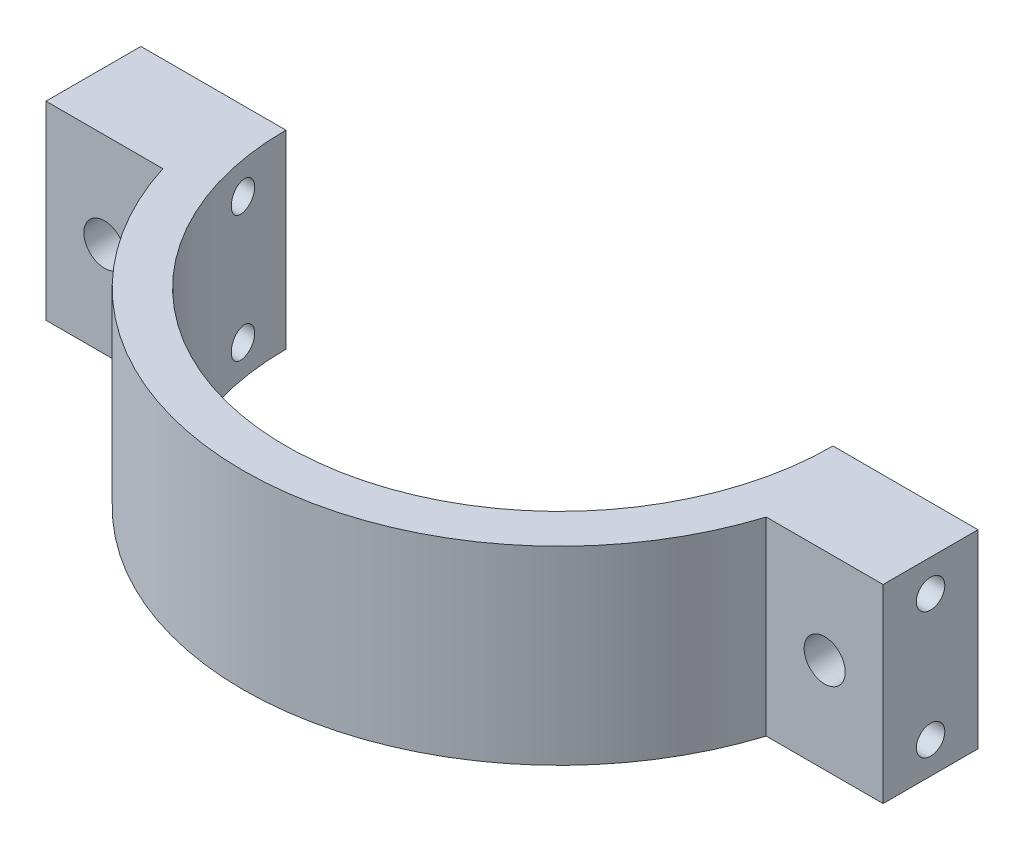
SolidWorks part; units mm, degrees
ref_plane "Front Plane" through (0, 0, 0) normal (0, 0, 1) x (1, 0, 0)
ref_plane "Top Plane" through (0, 0, 0) normal (0, 1, 0) x (1, 0, 0)
ref_plane "Right Plane" through (0, 0, 0) normal (1, 0, 0) x (0, 0, -1)
sketch "Sketch1" plane through (0, 0, 0) normal (0, 1, 0) x (1, 0, 0)
  line L0 (-43.25, 0) -> (-66.175, 0)
  line L4 (66.175, 0) -> (43.25, 0)
  line L5 (0, 0) -> (0, -67.037) construction
  line L6 (-66.175, 0) -> (-66.175, -15)
  line L7 (-66.175, -15) -> (-47.697, -15)
  line L8 (66.175, -15) -> (47.697, -15)
  line L9 (66.175, 0) -> (66.175, -15)
  circle A0 centre (0, 0) radius 43.25 construction
  arc A1 (-43.25, 0) -> (43.25, 0) centre (0, 0) ccw
  arc A2 (-47.697, -15) -> (47.697, -15) centre (0, 0) ccw
  point P14 (-45.8362, -19.976)
  dimension "D1" = 86.5
  dimension "D2" = 50
  dimension "D3" = 15
  dimension "D4" = 132.35
extrude "Boss-Extrude1" add sketch "Sketch1" along normal mid plane 30
sketch "Sketch2" plane through (0, 0, 15) normal (0, 0, 1) x (1, 0, 0)
  line L0 (-56.936, -15) -> (-56.936, 15) construction
  line L1 (-66.175, -15) -> (-47.697, -15) construction
  line L2 (-66.175, 15) -> (-47.697, 15) construction
  line L3 (0, 0) -> (0, 15) construction
  line L4 (47.697, 15) -> (-47.697, 15) construction
  circle A0 centre (-56.936, 0) radius 3.25
  circle A1 centre (56.936, 0) radius 3.25
  dimension "D1" = 6.5
extrude "Cut-Extrude1" cut sketch "Sketch2" against normal through all
sketch "Sketch3" plane through (-66.175, 0, 0) normal (-1, 0, 0) x (0, 0, 1)
  line L0 (7.5, 15) -> (7.5, -15) construction
  line L1 (0, 15) -> (15, 15) construction
  line L2 (0, -15) -> (15, -15) construction
  line L3 (15, 0) -> (0, 0) construction
  line L4 (15, 15) -> (15, -15) construction
  circle A0 centre (7.5, -10) radius 2.25
  circle A1 centre (7.5, 10) radius 2.25
  point P15 (7.5, -7.4267)
  point P16 (7.5, -9.1073)
  dimension "D1" = 20
  dimension "D2" = 4.5
extrude "Cut-Extrude2" cut sketch "Sketch3" against normal through all
